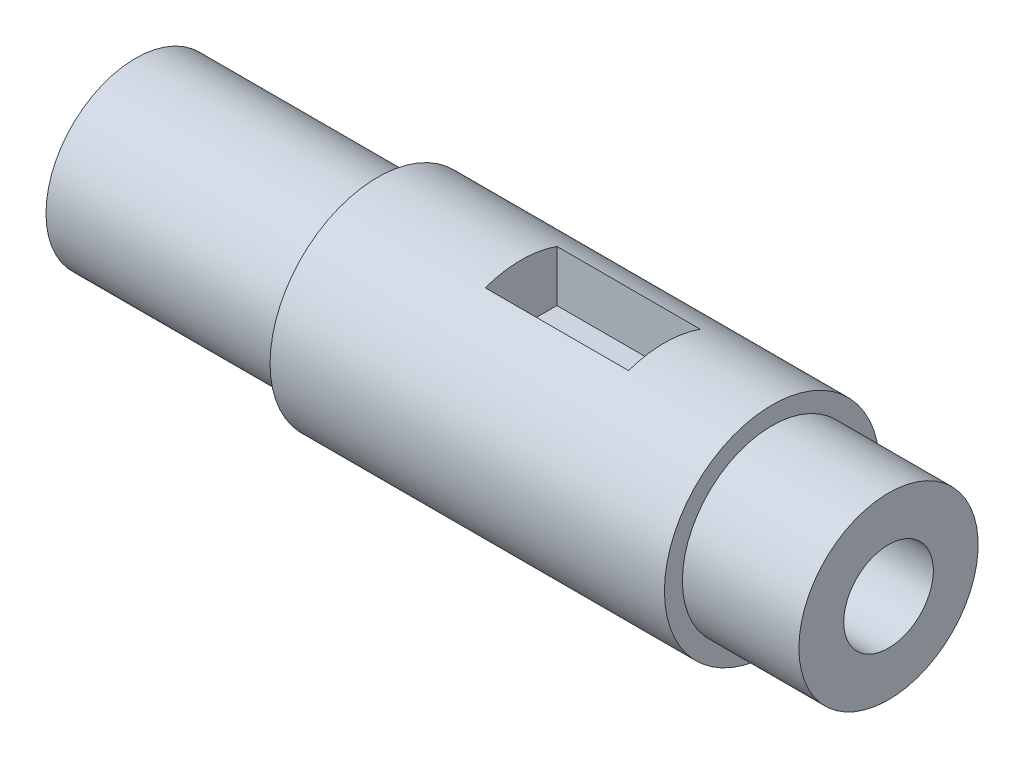
SolidWorks part; units mm, degrees
ref_plane "Front Plane" through (0, 0, 0) normal (0, 0, 1) x (1, 0, 0)
ref_plane "Top Plane" through (0, 0, 0) normal (0, 1, 0) x (1, 0, 0)
ref_plane "Right Plane" through (0, 0, 0) normal (1, 0, 0) x (0, 0, -1)
sketch "Sketch1" plane through (0, 0, 0) normal (0, 0, 1) x (1, 0, 0)
  line L0 (-21, 0) -> (21, 0) construction
  line L1 (-21, 2.5) -> (21, 2.5)
  line L2 (-21, 2.5) -> (-21, 5)
  line L3 (-21, 5) -> (-7.5, 5)
  line L4 (-7.5, 5) -> (-7.5, 6)
  line L5 (-7.5, 6) -> (14.5, 6)
  line L6 (21, 5) -> (21, 2.5)
  line L7 (3.5, 6) -> (3.5, 2.5) construction
  line L8 (14.5, 6) -> (14.5, 5)
  line L9 (14.5, 5) -> (21, 5)
  point P4 (0, 0)
  dimension "D1" = 13.5
  dimension "D2" = 11
  dimension "D3" = 10
  dimension "D4" = 5
  dimension "D5" = 12
  dimension "D6" = 6.5
  dimension "D7" = 10
revolve "Revolve1" add sketch "Sketch1" angle 360 about L0
ref_plane "Plane1" through (0, 6, 0) normal (0, 1, 0) x (1, 0, 0)
sketch "Sketch2" plane through (0, 6, 0) normal (0, 1, 0) x (1, 0, 0)
  line L0 (-7.5, 0) -> (14.5, 0) construction
  line L1 (-7.5, 5) -> (-7.5, -5) construction
  line L3 (14.5, -6) -> (14.5, 6) construction
  line L4 (0.5, -2) -> (8.5, -2)
  line L5 (0.5, -2) -> (0.5, 2)
  line L6 (0.5, 2) -> (8.5, 2)
  line L7 (8.5, -2) -> (8.5, 2)
  line L8 (0.5, -2) -> (8.5, 2) construction
  line L9 (0.5, 2) -> (8.5, -2) construction
  line L10 (-7.5, 6) -> (-7.5, -6) construction
  point P4 (14.5, 0)
  point P6 (4.5, 0)
  point P11 (0, 0)
  point P12 (0, 0)
  point P13 (0, 0)
  point P15 (0, 0)
  point P16 (0, 0)
  dimension "D1" = 8
  dimension "D2" = 4
  dimension "D3" = 8
extrude "Cut-Extrude1" cut sketch "Sketch2" against normal blind 3.2
